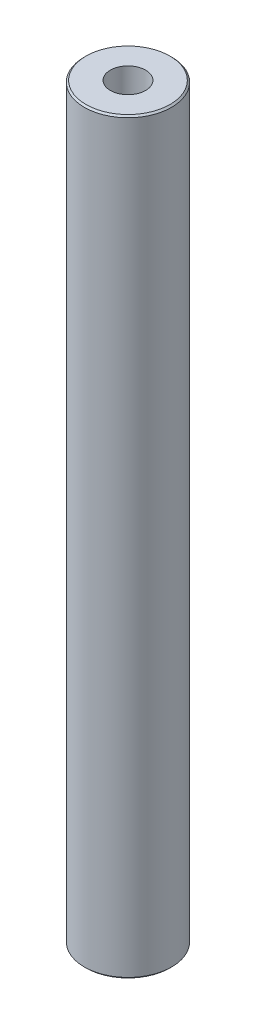
SolidWorks part; units mm, degrees
ref_plane "Front Plane" through (0, 0, 0) normal (0, 0, 1) x (1, 0, 0)
ref_plane "Top Plane" through (0, 0, 0) normal (0, 1, 0) x (1, 0, 0)
ref_plane "Right Plane" through (0, 0, 0) normal (1, 0, 0) x (0, 0, -1)
sketch "Sketch1" plane through (0, 0, 0) normal (0, 1, 0) x (1, 0, 0)
  circle A0 centre (0, 0) radius 35
  dimension "SHAFT_OD" = 70
extrude "Boss-Extrude1" add sketch "Sketch1" along normal blind 600
sketch "Sketch2" plane through (0, 0, 0) normal (0, 1, 0) x (1, 0, 0)
  circle A0 centre (0, 0) radius 14.1687
  dimension "BORE_D" = 28.3373
extrude "Cut-Extrude1" cut sketch "Sketch2" along normal through all
chamfer "Chamfer1" distance 1.3054 angle 45 2 edges at (0, 600, 35) (0, 0, 35)
